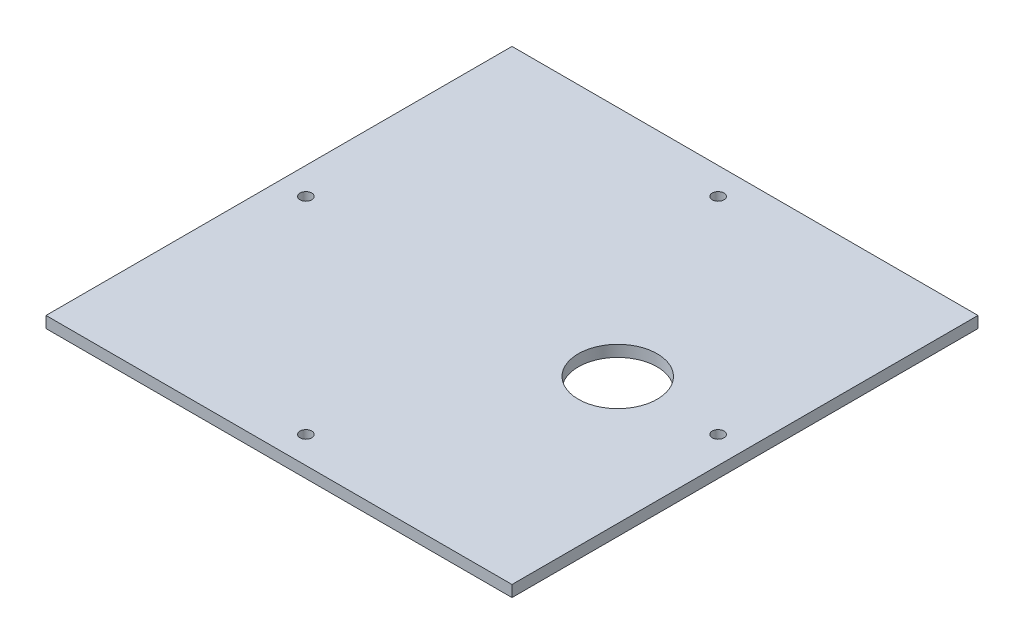
SolidWorks part; units mm, degrees
ref_plane "Front Plane" through (0, 0, 0) normal (0, 0, 1) x (1, 0, 0)
ref_plane "Top Plane" through (0, 0, 0) normal (0, 1, 0) x (1, 0, 0)
ref_plane "Right Plane" through (0, 0, 0) normal (1, 0, 0) x (0, 0, -1)
sketch "Sketch1" plane through (0, 0, 0) normal (0, 1, 0) x (1, 0, 0)
  line L1 (-60.5343, 65) -> (69.4657, 65)
  line L2 (-60.5343, 65) -> (-60.5343, -65)
  line L3 (-60.5343, -65) -> (69.4657, -65)
  line L4 (69.4657, 65) -> (69.4657, -65)
  line L5 (-60.5343, 65) -> (69.4657, -65) construction
  line L7 (-53.0343, 57.5) -> (61.9657, 57.5) construction
  line L8 (-53.0343, 57.5) -> (-53.0343, -57.5) construction
  line L9 (-53.0343, -57.5) -> (61.9657, -57.5) construction
  line L10 (61.9657, 57.5) -> (61.9657, -57.5) construction
  line L11 (-53.0343, 57.5) -> (61.9657, -57.5) construction
  circle A0 centre (-53.0343, 0) radius 1.65
  circle A1 centre (4.4657, 57.5) radius 1.65
  circle A2 centre (61.9657, 0) radius 1.65
  circle A3 centre (4.4657, -57.5) radius 1.65
  circle A13 centre (33.9657, 0) radius 11
  point P0 (4.4657, 0)
  point P5 (0, 0)
  point P6 (4.4657, 0)
  point P37 (0, 0)
  point P38 (0, 0)
  dimension "D6" = 22
  dimension "D17" = 28
  dimension "D1" = 7.5
  dimension "D2" = 7.5
  dimension "D3" = 130
  dimension "D4" = 130
extrude "Boss-Extrude1" add sketch "Sketch1" along normal blind 3.175
